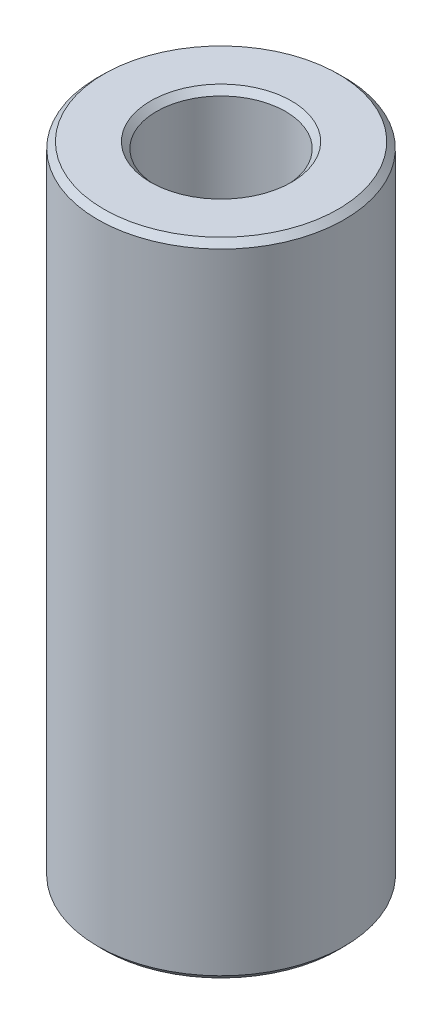
SolidWorks part; units mm, degrees
ref_plane "Front Plane" through (0, 0, 0) normal (0, 0, 1) x (1, 0, 0)
ref_plane "Top Plane" through (0, 0, 0) normal (0, 1, 0) x (1, 0, 0)
ref_plane "Right Plane" through (0, 0, 0) normal (1, 0, 0) x (0, 0, -1)
sketch "Sketch1" plane through (0, 0, 0) normal (0, 1, 0) x (1, 0, 0)
  circle A0 centre (0, 0) radius 10
  dimension "SLEEVE_OD" = 20
extrude "Boss-Extrude1" add sketch "Sketch1" along normal blind 52.0294
sketch "Sketch2" plane through (0, 0, 0) normal (0, 1, 0) x (1, 0, 0)
  circle A0 centre (0, 0) radius 5.2343
  dimension "BORE_D" = 10.4686
extrude "Cut-Extrude1" cut sketch "Sketch2" along normal through all
chamfer "Chamfer1" distance 0.4833 angle 45.745 4 edges at (0, 52.0294, 5.2343) (0, 0, 5.2343) (0, 0, 10) (0, 52.0294, 10) first distance on face at (0, 52.0294, 5.2343) first distance on face at (0, 0, 5.2343) first distance on face at (0, 52.0294, 10)
